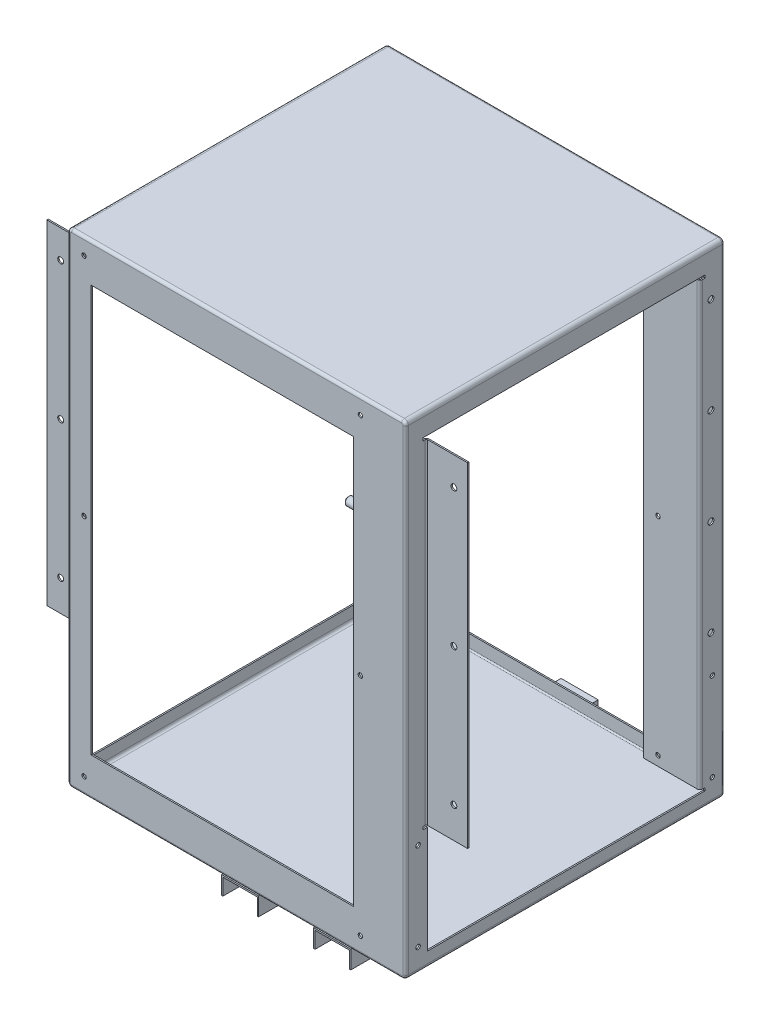
SolidWorks part; units mm, degrees
ref_plane "Спереди" through (0, 0, 0) normal (0, 0, 1) x (1, 0, 0)
ref_plane "Сверху" through (0, 0, 0) normal (0, 1, 0) x (1, 0, 0)
ref_plane "Справа" through (0, 0, 0) normal (1, 0, 0) x (0, 0, -1)
sketch "Эскиз1" plane through (0, 0, 0) normal (0, 0, 1) x (1, 0, 0)
  line L0 (-33.8044, 0) -> (37.3961, 0) construction
  line L1 (0, -31.1634) -> (0, 34.1213) construction
  line L3 (-120, -175) -> (120, -175)
  line L4 (-122, -173) -> (-122, 173)
  line L5 (-120, 175) -> (120, 175)
  line L6 (122, -173) -> (122, 173)
  arc A0 (-122, 173) -> (-120, 175) centre (-120, 173) cw
  arc A1 (120, 175) -> (122, 173) centre (120, 173) cw
  arc A2 (-120, -175) -> (-122, -173) centre (-120, -173) cw
  arc A3 (120, -175) -> (122, -173) centre (120, -173) ccw
  point P11 (-122, 175)
  point P14 (122, 175)
  point P17 (-122, -175)
  dimension "D3" = 2
  dimension "D1" = 350
  dimension "D2" = 244
extrude "Вытянуть-Тонкостенный1" add sketch "Эскиз1" along normal blind 232 thin thin type one direction wall 1
sketch "Эскиз2" plane through (123, 0, 0) normal (1, 0, 0) x (0, 0, -1)
  line L0 (-232, 176) -> (0, 176) construction
  line L1 (-216, -165) -> (-16, -165)
  line L2 (-216, -165) -> (-216, 160)
  line L3 (-216, 160) -> (-16, 160)
  line L4 (-16, -165) -> (-16, 160)
  line L5 (-116, 208.5566) -> (-116, -206.9252) construction
  line L6 (-232, -173) -> (-232, 173) construction
  line L7 (0, -173) -> (0, 173) construction
  dimension "D1" = 200
  dimension "D2" = 325
  dimension "D3" = 16
extrude "Вырез-Вытянуть1" cut sketch "Эскиз2" against normal blind 500
sketch "Эскиз3" plane through (0, 0, 232) normal (0, 0, 1) x (1, 0, 0)
  line L4 (-123, 173) -> (-123, -173)
  line L5 (-120, -176) -> (120, -176)
  line L6 (123, -173) -> (123, 173)
  line L7 (120, 176) -> (-120, 176)
  line L8 (-123, 173) -> (-123, -173)
  line L9 (-120, -176) -> (120, -176)
  line L10 (123, -173) -> (123, 173)
  line L11 (120, 176) -> (-120, 176)
  arc A4 (-120, 176) -> (-123, 173) centre (-120, 173) ccw
  arc A5 (-123, -173) -> (-120, -176) centre (-120, -173) ccw
  arc A6 (120, -176) -> (123, -173) centre (120, -173) ccw
  arc A7 (123, 173) -> (120, 176) centre (120, 173) ccw
  arc A8 (-120, 176) -> (-123, 173) centre (-120, 173) ccw
  arc A9 (-123, -173) -> (-120, -176) centre (-120, -173) ccw
  arc A10 (120, -176) -> (123, -173) centre (120, -173) ccw
  arc A11 (123, 173) -> (120, 176) centre (120, 173) ccw
  dimension "D1" = 0
extrude "Вытянуть1" add sketch "Эскиз3" against normal blind 1
sketch "Эскиз4" plane through (0, 0, 0) normal (0, 0, -1) x (-1, 0, 0)
  line L1 (0, 0) -> (0, 114.475) construction
  line L3 (-107, -165) -> (107, -165)
  line L4 (120, 176) -> (-120, 176)
  line L5 (-123, 173) -> (-123, -173)
  line L6 (-120, -176) -> (120, -176)
  line L7 (123, -173) -> (123, 173)
  line L8 (120, 176) -> (-120, 176)
  line L9 (-123, 173) -> (-123, -173)
  line L10 (-120, -176) -> (120, -176)
  line L11 (123, -173) -> (123, 173)
  line L12 (-107, -165) -> (-107, 160)
  line L13 (-107, 160) -> (107, 160)
  line L14 (107, -165) -> (107, 160)
  arc A4 (123, 173) -> (120, 176) centre (120, 173) ccw
  arc A5 (-120, 176) -> (-123, 173) centre (-120, 173) ccw
  arc A6 (-123, -173) -> (-120, -176) centre (-120, -173) ccw
  arc A7 (120, -176) -> (123, -173) centre (120, -173) ccw
  arc A8 (123, 173) -> (120, 176) centre (120, 173) ccw
  arc A9 (-120, 176) -> (-123, 173) centre (-120, 173) ccw
  arc A10 (-123, -173) -> (-120, -176) centre (-120, -173) ccw
  arc A11 (120, -176) -> (123, -173) centre (120, -173) ccw
  dimension "D2" = 214
  dimension "D3" = 325
  dimension "D4" = 16
  dimension "D1" = 0
extrude "Вытянуть2" add sketch "Эскиз4" against normal blind 1
fillet "Скругление1" radius 1 16 edges at (121.4142, 174.4142, 231) (122, 0, 231) (121.4142, -174.4142, 231) (0, -175, 231) (-121.4142, -174.4142, 231) (-122, 0, 231) (-121.4142, 174.4142, 231) (-121.4142, 174.4142, 1) (-122, 0, 1) (-121.4142, -174.4142, 1) (0, -175, 1) (121.4142, -174.4142, 1) (122, 0, 1) (121.4142, 174.4142, 1) (0, 175, 231) (0, 175, 1)
fillet "Скругление2" radius 2 16 edges at (-122.1213, 175.1213, 232) (0, 176, 232) (122.1213, 175.1213, 232) (123, 0, 232) (122.1213, -175.1213, 232) (0, -176, 232) (-122.1213, -175.1213, 232) (-122.1213, 175.1213, 0) (0, 176, 0) (122.1213, 175.1213, 0) (123, 0, 0) (122.1213, -175.1213, 0) (0, -176, 0) (-122.1213, -175.1213, 0) (-123, 0, 232) (-123, 0, 0)
sketch "Эскиз5" plane through (123, 0, 0) normal (1, 0, 0) x (0, 0, -1)
  line L1 (-232, -173) -> (-232, 173) construction
  line L2 (-116, 217.3911) -> (-116, -53.3101) construction
  line L3 (0, 173) -> (0, -173) construction
  line L4 (-10, -67.5) -> (-10, 2.5) construction
  line L5 (-10, 2.5) -> (-10, 72.5) construction
  line L6 (-10, 72.5) -> (-10, 142.5) construction
  line L8 (-230, 176) -> (-2, 176) construction
  circle A4 centre (-10, 142.5) radius 2.15
  circle A5 centre (-10, 72.5) radius 2.15
  circle A6 centre (-10, 2.5) radius 2.15
  circle A7 centre (-10, -67.5) radius 2.15
  dimension "D1" = 106
  dimension "D2" = 70
  dimension "D4" = 70
  dimension "D5" = 4.3
  dimension "D6" = 33.5
  dimension "D3" = 70
extrude "Вырез-Вытянуть2" cut sketch "Эскиз5" against normal blind 500
sketch "Эскиз6" plane through (-123, 0, 0) normal (-1, 0, 0) x (0, 0, 1)
  line L0 (230, -176) -> (2, -176) construction
  line L1 (16, -165) -> (16, 160) construction
  circle A0 centre (8, -118) radius 3
  dimension "D1" = 6
  dimension "D3" = 8
  dimension "D2" = 58
extrude "Вытянуть3" add sketch "Эскиз6" along normal blind 20
chamfer "Фаска1" distance 1 angle 45 1 edges at (-143, -118, 11)
sketch "Эскиз7" plane through (-123, 0, 0) normal (-1, 0, 0) x (0, 0, 1)
  line L0 (9, -170.4186) -> (9, -98.725) construction
  line L1 (230, -176) -> (2, -176) construction
  line L2 (0, -173) -> (0, 173) construction
  line L3 (116, 41.2045) -> (116, -219.7788) construction
  line L6 (16, -165) -> (16, 160) construction
  line L7 (216, 160) -> (216, -165) construction
  circle A0 centre (9, -95) radius 1.6
  circle A1 centre (9, -159) radius 1.6
  circle A2 centre (223, -95) radius 1.6
  circle A3 centre (223, -159) radius 1.6
  dimension "D4" = 3.2
  dimension "D1" = 17
  dimension "D2" = 81
  dimension "D3" = 9
extrude "Вырез-Вытянуть3" cut sketch "Эскиз7" against normal blind 500
sketch "Эскиз8" plane through (0, 0, 232) normal (0, 0, 1) x (1, 0, 0)
  line L0 (-123, -173) -> (-123, 173) construction
  line L1 (-106, -148) -> (85, -148)
  line L2 (-106, -148) -> (-106, 148)
  line L3 (-106, 148) -> (85, 148)
  line L4 (85, -148) -> (85, 148)
  line L5 (-120, 176) -> (120, 176) construction
  line L6 (120, -176) -> (-120, -176) construction
  line L7 (123, 173) -> (123, -173) construction
  dimension "D1" = 17
  dimension "D2" = 28
  dimension "D3" = 28
  dimension "D4" = 38
extrude "Вырез-Вытянуть4" cut sketch "Эскиз8" against normal blind 2
sketch "Эскиз9" plane through (0, 0, 232) normal (0, 0, 1) x (1, 0, 0)
  line L0 (-120, 176) -> (120, 176) construction
  line L1 (-123, -173) -> (-123, 173) construction
  line L2 (0, 0) -> (-174.4696, 0) construction
  line L3 (-10.5, 126.3418) -> (-10.5, -63.6186) construction
  line L4 (120, -176) -> (-120, -176) construction
  line L5 (-106, 148) -> (-106, -148) construction
  line L6 (85, -148) -> (85, 148) construction
  circle A0 centre (-111, 164) radius 1.6
  circle A1 centre (-111, 0) radius 1.6
  circle A2 centre (-111, -164) radius 1.6
  circle A3 centre (90, -164) radius 1.6
  circle A4 centre (90, 0) radius 1.6
  circle A5 centre (90, 164) radius 1.6
  dimension "D1" = 12
  dimension "D3" = 3.2
  dimension "D4" = 3.2
  dimension "D2" = 12
  dimension "D5" = 12
extrude "Вырез-Вытянуть5" cut sketch "Эскиз9" against normal blind 2
sketch "Эскиз10" plane through (123, 0, 0) normal (0, 0, 1) x (1, 0, 0)
  line L0 (-134, -176.0152) -> (-134, -175.8152)
  line L1 (-134, -189.0152) -> (-134, -176.0152)
  line L2 (-133, -189.0152) -> (-133, -177.0152)
  line L3 (-133, -177.0152) -> (-108, -177.0152)
  line L4 (-108, -189.0152) -> (-108, -177.0152)
  line L5 (-107, -175.8152) -> (-134, -175.8152)
  line L6 (-67, -176.0152) -> (-67, -175.8152)
  line L7 (-107, -189.0152) -> (-107, -176.0152)
  line L8 (-134, -189.0152) -> (-133, -189.0152)
  line L9 (-108, -189.0152) -> (-107, -189.0152)
  line L10 (-87, -139.0452) -> (-87, -213.9051) construction
  line L11 (-66, -189.0152) -> (-67, -189.0152)
  line L12 (-40, -189.0152) -> (-41, -189.0152)
  line L13 (-67, -189.0152) -> (-67, -176.0152)
  line L14 (-67, -175.8152) -> (-40, -175.8152)
  line L15 (-66, -189.0152) -> (-66, -177.0152)
  line L16 (-41, -177.0152) -> (-66, -177.0152)
  line L17 (-41, -189.0152) -> (-41, -177.0152)
  line L18 (-40, -189.0152) -> (-40, -176.0152)
  line L19 (-40, -176.0152) -> (-40, -175.8152)
  line L20 (0, 173) -> (0, -173) construction
  line L21 (-107, -176.0152) -> (-107, -175.8152)
  line L25 (-134, -176.0152) -> (-107, -176.0152) construction
  dimension "D1" = 40
  dimension "D2" = 12
  dimension "D3" = 25
  dimension "D4" = 12
  dimension "D6" = 20
  dimension "D5" = 1
extrude "Вытянуть6" add sketch "Эскиз10" along normal up to surface (232 mm away) and the other way blind 15 up to face at (88.4, 164, 232)
sketch "Эскиз11" plane through (123, 0, 0) normal (1, 0, 0) x (0, 0, -1)
  line L0 (-216, 160) -> (-216, -165) construction
  line L1 (-216, 158) -> (-217, 158)
  line L2 (-216, 158) -> (-216, -85)
  line L3 (-216, -85) -> (-217, -85)
  line L4 (-217, 158) -> (-217, -85)
  line L5 (-16, 160) -> (-216, 160) construction
  line L11 (-232, -173) -> (-232, 173) construction
  line L12 (-230, 176) -> (-2, 176) construction
  dimension "D1" = 2
  dimension "D2" = 261
  dimension "D3" = 15
extrude "Вытянуть7" add sketch "Эскиз11" along normal blind 30
sketch "Эскиз12" plane through (123, 0, 0) normal (1, 0, 0) x (0, 0, -1)
  line L0 (-217, 158) -> (-216, 158) construction
  line L1 (-216, 160) -> (-219.5, 160)
  line L2 (-216, 160) -> (-216, 158)
  line L3 (-216, 158) -> (-219.5, 158)
  line L4 (-219.5, 160) -> (-219.5, 158)
  line L5 (-16, 160) -> (-216, 160) construction
  line L6 (-216, -85) -> (-217, -85) construction
  line L7 (-216, -85) -> (-219.5, -85)
  line L8 (-216, -85) -> (-216, -87)
  line L9 (-216, -87) -> (-219.5, -87)
  line L10 (-219.5, -85) -> (-219.5, -87)
  dimension "D1" = 3.5
  dimension "D2" = 3.5
  dimension "D3" = 2
extrude "Вырез-Вытянуть6" cut sketch "Эскиз12" against normal blind 20
sketch "Эскиз13" plane through (-123, 0, 0) normal (-1, 0, 0) x (0, 0, 1)
  line L4 (216, 158) -> (216, -85)
  line L5 (217, 158) -> (216, 158)
  line L6 (217, -85) -> (217, 158)
  line L7 (216, -85) -> (217, -85)
  line L8 (216, 158) -> (216, -85)
  line L9 (217, 158) -> (216, 158)
  line L10 (217, -85) -> (217, 158)
  line L11 (216, -85) -> (217, -85)
  dimension "D1" = 0
extrude "Вытянуть8" add sketch "Эскиз13" along normal blind 30
sketch "Эскиз14" plane through (0, 0, 216) normal (0, 0, -1) x (-1, 0, 0)
  line L0 (-143, 137.5) -> (-143, -64.2604) construction
  line L1 (-153, -85) -> (-153, 158) construction
  line L2 (-153, -85) -> (-122, -85) construction
  line L3 (0, 0) -> (0, 67.9896) construction
  circle A0 centre (-143, 137.5) radius 2.15
  circle A1 centre (-143, 37.5) radius 2.15
  circle A2 centre (-143, -62.5) radius 2.15
  circle A3 centre (143, -62.5) radius 2.15
  circle A4 centre (143, 37.5) radius 2.15
  circle A5 centre (143, 137.5) radius 2.15
  dimension "D1" = 100
  dimension "D2" = 100
  dimension "D4" = 22.5
  dimension "D5" = 4.3
  dimension "D3" = 10
extrude "Вырез-Вытянуть7" cut sketch "Эскиз14" against normal blind 30
sketch "Эскиз16" plane through (0, 0, 16) normal (0, 0, 1) x (1, 0, 0)
  line L4 (122, 160) -> (122, -165)
  line L5 (122, -165) -> (123, -165)
  line L6 (123, -165) -> (123, 160)
  line L7 (123, 160) -> (122, 160)
  line L8 (122, 160) -> (122, -165)
  line L9 (122, -165) -> (123, -165)
  line L10 (123, -165) -> (123, 160)
  line L11 (123, 160) -> (122, 160)
  line L12 (-123, -165) -> (-122, -165)
  line L13 (-122, -165) -> (-122, 160)
  line L14 (-122, 160) -> (-123, 160)
  line L15 (-123, 160) -> (-123, -165)
  line L16 (-123, -165) -> (-122, -165)
  line L17 (-122, -165) -> (-122, 160)
  line L18 (-122, 160) -> (-123, 160)
  line L19 (-123, 160) -> (-123, -165)
  dimension "D1" = 0
  dimension "D2" = 0
extrude "Вытянуть9" add sketch "Эскиз16" along normal blind 2
sketch "Эскиз17" plane through (122, 0, 0) normal (-1, 0, 0) x (0, 0, 1)
  line L0 (18, 160) -> (18, -165) construction
  line L1 (18, -165) -> (216, -165) construction
  line L2 (18, -163) -> (17, -163)
  line L3 (18, -163) -> (18, 158)
  line L4 (18, 158) -> (17, 158)
  line L5 (17, -163) -> (17, 158)
  line L6 (219.5, 160) -> (18, 160) construction
  dimension "D1" = 1
  dimension "D2" = 2
  dimension "D3" = 2
extrude "Вытянуть10" add sketch "Эскиз17" along normal blind 40
sketch "Эскиз18" plane through (-122, 0, 0) normal (1, 0, 0) x (0, 0, -1)
  line L4 (-18, 158) -> (-18, -163)
  line L5 (-17, 158) -> (-18, 158)
  line L6 (-17, -163) -> (-17, 158)
  line L7 (-18, -163) -> (-17, -163)
  line L8 (-18, 158) -> (-18, -163)
  line L9 (-17, 158) -> (-18, 158)
  line L10 (-17, -163) -> (-17, 158)
  line L11 (-18, -163) -> (-17, -163)
  dimension "D1" = 0
extrude "Вытянуть11" add sketch "Эскиз18" along normal blind 40
sketch "Эскиз19" plane through (-122, 0, 0) normal (1, 0, 0) x (0, 0, -1)
  line L0 (-117, -114.6313) -> (-117, 83.3784) construction
  line L1 (-18, -165) -> (-14.5, -165)
  line L2 (-18, -165) -> (-18, -163)
  line L3 (-18, -163) -> (-14.5, -163)
  line L4 (-14.5, -165) -> (-14.5, -163)
  line L5 (-18, 160) -> (-14.5, 160)
  line L6 (-18, 160) -> (-18, 158)
  line L7 (-18, 158) -> (-14.5, 158)
  line L8 (-14.5, 160) -> (-14.5, 158)
  line L9 (-18, -165) -> (-18, 160) construction
  line L10 (-216, -87) -> (-216, -165) construction
  line L12 (-216, -85) -> (-219.5, -85)
  line L13 (-216, -85) -> (-216, -87)
  line L14 (-216, -87) -> (-219.5, -87)
  line L15 (-219.5, 160) -> (-219.5, 158)
  line L16 (-216, 158) -> (-219.5, 158)
  line L17 (-216, 160) -> (-216, 158)
  line L18 (-216, 160) -> (-219.5, 160)
  line L19 (-219.5, -85) -> (-219.5, -87)
  dimension "D1" = 3.5
  dimension "D2" = 2
  dimension "D3" = 2
  dimension "D4" = 3.5
  dimension "D5" = 2
  dimension "D6" = 3.5
extrude "Вырез-Вытянуть8" cut sketch "Эскиз19" against normal blind 40
sketch "Эскиз20" plane through (0, 0, 17) normal (0, 0, -1) x (-1, 0, 0)
  line L0 (0, 0) -> (0, 229.3247) construction
  line L1 (-92.5, 145.5) -> (-92.5, -135.839) construction
  line L2 (-120, 176) -> (120, 176) construction
  circle A0 centre (-92.5, 145.5) radius 1.6
  circle A1 centre (-92.5, -5.25) radius 1.6
  circle A2 centre (-92.5, -156) radius 1.6
  circle A3 centre (92.5, -156) radius 1.6
  circle A4 centre (92.5, -5.25) radius 1.6
  circle A5 centre (92.5, 145.5) radius 1.6
  dimension "D1" = 301.5
  dimension "D3" = 30.5
  dimension "D4" = 3.2
  dimension "D5" = 150.75
  dimension "D2" = 92.5
extrude "Вырез-Вытянуть9" cut sketch "Эскиз20" against normal blind 10
sketch "Эскиз21" plane through (0, 0, 17) normal (0, 0, -1) x (-1, 0, 0)
  line L0 (92, 106.0183) -> (92, 38.6212) construction
  line L1 (82, -163) -> (82, 158) construction
  circle A0 centre (92, 110.7) radius 2.15
  circle A1 centre (92, 84.7) radius 2.15
  circle A2 centre (92.5, 145.5) radius 1.6 construction
  dimension "D2" = 26
  dimension "D3" = 34.8
  dimension "D4" = 4.3
  dimension "D1" = 10
extrude "Вырез-Вытянуть10" cut sketch "Эскиз21" against normal blind 10
fillet "Скругление3" radius 1 4 edges at (122, -2.5, 17) (-122, -2.5, 17) (-123, 36.5, 217) (123, 36.5, 217)
fillet "Скругление4" radius 2 4 edges at (122, 36.5, 216) (123, -2.5, 18) (-123, -2.5, 18) (-122, 36.5, 216)
sketch "Эскиз22" plane through (122, 0, 0) normal (-1, 0, 0) x (0, 0, 1)
  line L1 (14.5, -165) -> (19.251, -165)
  line L2 (14.5, -165) -> (14.5, -162.9892)
  line L3 (14.5, -162.9892) -> (19.251, -162.9892)
  line L4 (19.251, -165) -> (19.251, -162.9892)
  line L5 (17.7321, 160) -> (14.2321, 160)
  line L6 (17.7321, 160) -> (17.7321, 158)
  line L7 (17.7321, 158) -> (14.2321, 158)
  line L8 (14.2321, 160) -> (14.2321, 158)
  dimension "D1" = 2
  dimension "D2" = 3.5
extrude "Вырез-Вытянуть11" cut sketch "Эскиз22" against normal blind 10
